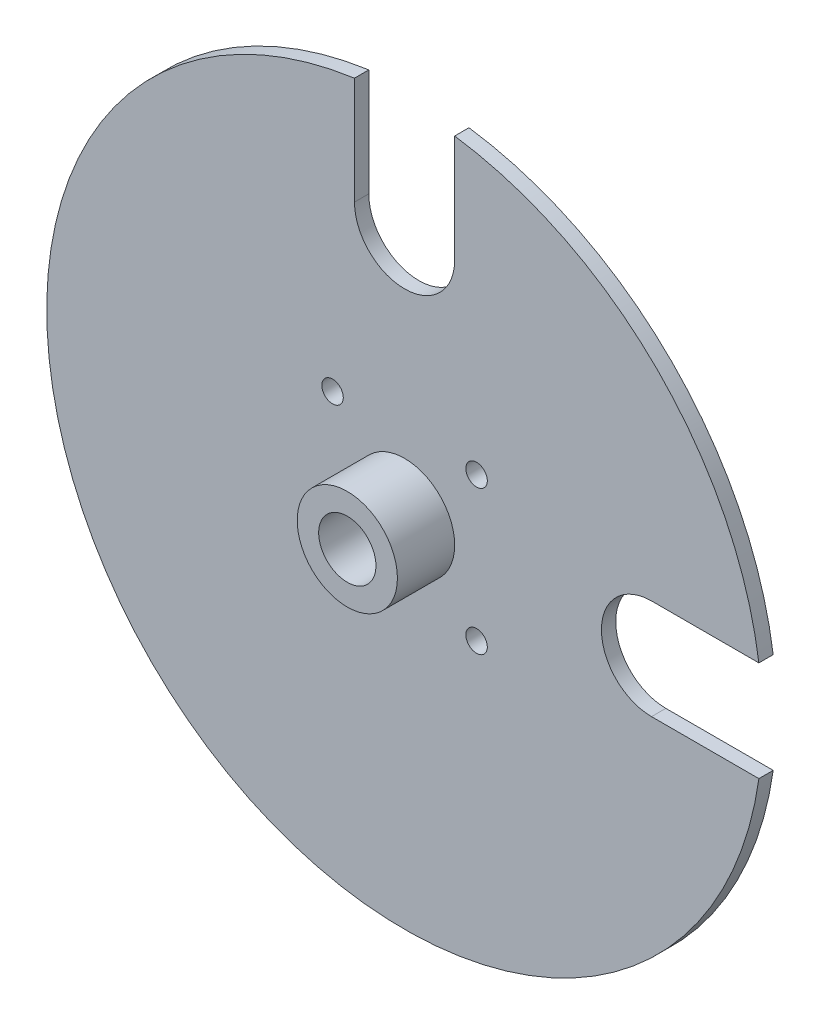
SolidWorks part; units mm, degrees
ref_plane "Front Plane" through (0, 0, 0) normal (0, 0, 1) x (1, 0, 0)
ref_plane "Top Plane" through (0, 0, 0) normal (0, 1, 0) x (1, 0, 0)
ref_plane "Right Plane" through (0, 0, 0) normal (1, 0, 0) x (0, 0, -1)
sketch "Sketch1" plane through (0, 0, 0) normal (0, 0, 1) x (1, 0, 0)
  line L0 (0, 0) -> (0, 22.0431) construction
  line L1 (0, 22.0431) -> (0, -27.0486) construction
  line L2 (0, -27.0486) -> (0, -2.5028) construction
  line L3 (0, 0) -> (34.3402, 0) construction
  line L4 (34.3402, 0) -> (-48.5021, 0) construction
  line L5 (0, 0) -> (-22.0431, 22.0431) construction
  circle A0 centre (0, 0) radius 4
  circle A1 centre (0, 0) radius 20
  circle A2 centre (-10.062, 10.062) radius 1.5
  circle A3 centre (10.062, 10.062) radius 1.5
  circle A4 centre (10.062, -10.062) radius 1.5
  circle A5 centre (-10.062, -10.062) radius 1.5
  dimension "D1" = 8
  dimension "D2" = 40
  dimension "D3" = 3
extrude "Boss-Extrude1" add sketch "Sketch1" along normal blind 5
sketch "Sketch2" plane through (0, 0, 5) normal (0, 0, 1) x (1, 0, 0)
  circle A0 centre (0, 0) radius 4
  circle A1 centre (0, 0) radius 7
  dimension "D2" = 8
  dimension "D1" = 3
extrude "Boss-Extrude2" add sketch "Sketch2" along normal blind 10
sketch "Sketch3" plane through (0, 0, 5) normal (0, 0, 1) x (1, 0, 0)
  circle A0 centre (0, 0) radius 50
  circle A1 centre (0, 0) radius 4
  dimension "D1" = 100
extrude "Boss-Extrude3" add sketch "Sketch3" along normal blind 2
sketch "Sketch4" plane through (0, 0, 7) normal (0, 0, 1) x (1, 0, 0)
  line L0 (0, 0) -> (0, 27.5076) construction
  line L1 (-7, 49.5076) -> (-7, 34.5076)
  line L2 (49.5076, -7) -> (34.5076, -7)
  line L3 (7, 49.5076) -> (7, 34.5076)
  line L4 (0, 49.5076) -> (0, 50) construction
  line L5 (49.5076, 7) -> (34.5076, 7)
  circle A0 centre (0, 0) radius 50 construction
  arc A1 (7, 49.5076) -> (-7, 49.5076) centre (0, 0) ccw
  arc A2 (-7, 34.5076) -> (7, 34.5076) centre (0, 34.5076) ccw
  arc A3 (34.5076, 7) -> (34.5076, -7) centre (34.5076, 0) ccw
  arc A4 (49.5076, -7) -> (49.5076, 7) centre (0, 0) ccw
  point P11 (0, 34.5076)
  point P22 (0, 0)
  point P42 (0, 0)
  dimension "D1" = 7
  dimension "D2" = 15
  dimension "D3" = 2
extrude "Cut-Extrude1" cut sketch "Sketch4" against normal blind 2
sketch "Sketch5" plane through (0, 0, 0) normal (0, 0, -1) x (-1, 0, 0)
  circle A0 centre (-10.062, 10.062) radius 1.5
  circle A1 centre (-10.062, -10.062) radius 1.5
  circle A2 centre (10.062, 10.062) radius 1.5
  circle A3 centre (10.062, -10.062) radius 1.5
extrude "Cut-Extrude2" cut sketch "Sketch5" against normal through all both and the other way through all
